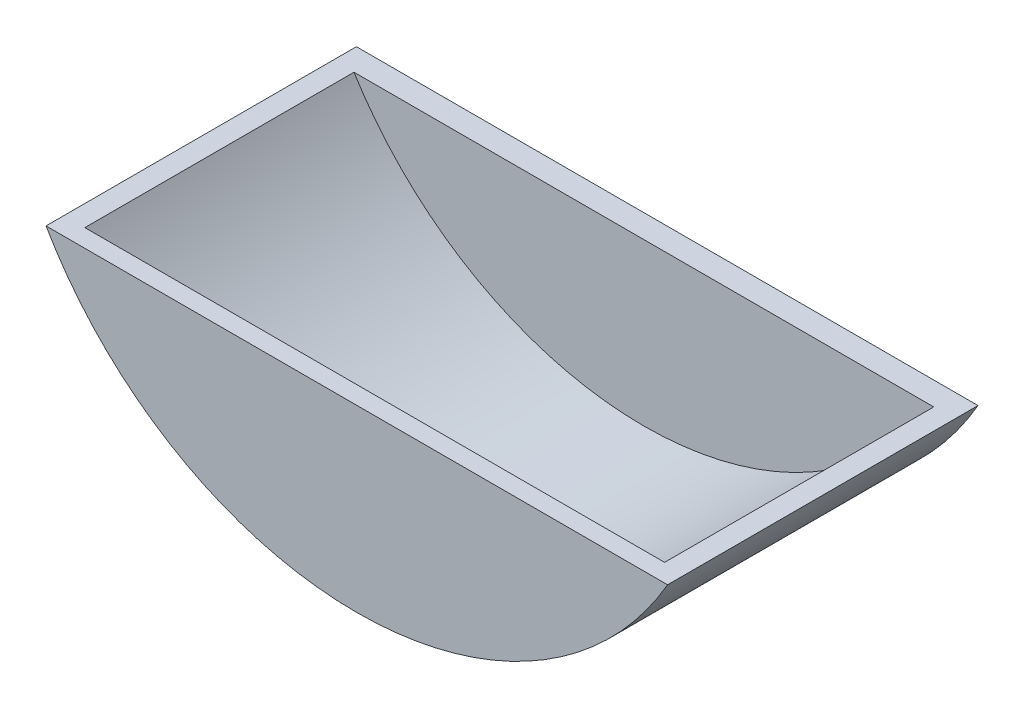
SolidWorks part; units mm, degrees
ref_plane "前视基准面" through (0, 0, 0) normal (0, 0, 1) x (1, 0, 0)
ref_plane "上视基准面" through (0, 0, 0) normal (0, 1, 0) x (1, 0, 0)
ref_plane "右视基准面" through (0, 0, 0) normal (1, 0, 0) x (0, 0, -1)
sketch "草图1" plane through (0, 0, 0) normal (0, 0, 1) x (1, 0, 0)
  line L1 (0, -100) -> (173.2051, -100)
  line L2 (173.2051, -100) -> (-173.2051, -100)
  arc A0 (-173.2051, -100) -> (173.2051, -100) centre (0, 0) ccw
  arc A2 (-161.5549, -100) -> (161.5549, -100) centre (0, 0) ccw
extrude "凸台-拉伸2" add sketch "草图1" along normal blind 150 contours L2 A0 L1 region at (167.38, -103.6056, 0)
sketch "草图2" plane through (0, 0, 0) normal (0, 0, -1) x (-1, 0, 0)
  line L0 (-173.2051, -100) -> (173.2051, -100)
  arc A0 (-173.2051, -100) -> (173.2051, -100) centre (0, 0) ccw
extrude "凸台-拉伸3" add sketch "草图2" along normal blind 13
sketch "草图3" plane through (0, 0, 150) normal (0, 0, 1) x (1, 0, 0)
  line L0 (-173.2051, -100) -> (173.2051, -100)
  arc A0 (-173.2051, -100) -> (173.2051, -100) centre (0, 0) ccw
extrude "凸台-拉伸4" add sketch "草图3" along normal blind 10
sketch "草图4" plane through (0, 0, -13) normal (0, 0, -1) x (-1, 0, 0)
  line L0 (0, 0) -> (0, -211.2543)
  line L8 (-25, -150.2939) -> (25, -150.2939)
  line L9 (-25, -150.2939) -> (-25, -136.2939)
  line L10 (-25, -136.2939) -> (25, -136.2939)
  line L11 (25, -150.2939) -> (25, -136.2939)
  line L12 (-25, -150.2939) -> (25, -136.2939) construction
  line L13 (-25, -136.2939) -> (25, -150.2939) construction
  point P3 (0, -147.0628)
  point P8 (0, -143.2939)
extrude "切除-拉伸1" cut sketch "草图4" against normal blind 10 contours L10 L9 L8 L0 | L8 L11 L10 L0 region at (-12.5, -143.2939, -13) region at (12.5, -143.2939, -13)
fillet "圆角1" radius 15 1 edges at (0, -136.2939, -3)
fillet "圆角2" radius 3 1 edges at (0, -136.2939, -13)
fillet "圆角3" radius 1 3 edges at (0, -150.2939, -13) (-25, -142.3028, -13) (25, -142.3028, -13)
